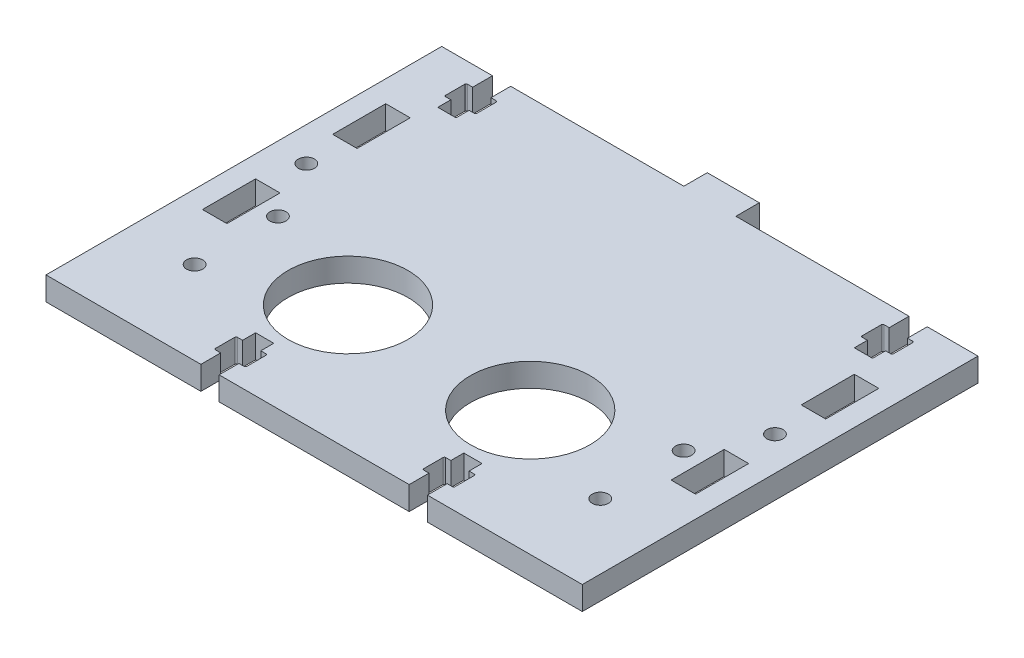
SolidWorks part; units mm, degrees
ref_plane "Front Plane" through (0, 0, 0) normal (0, 0, 1) x (1, 0, 0)
ref_plane "Top Plane" through (0, 0, 0) normal (0, 1, 0) x (1, 0, 0)
ref_plane "Right Plane" through (0, 0, 0) normal (1, 0, 0) x (0, 0, -1)
sketch "Sketch1" plane through (0, 0, 0) normal (0, 1, 0) x (1, 0, 0)
  line L1 (-51.5, 38) -> (51.5, 38)
  line L2 (-51.5, 38) -> (-51.5, -38)
  line L3 (-51.5, -38) -> (51.5, -38)
  line L4 (51.5, 38) -> (51.5, -38)
  line L5 (-51.5, 38) -> (51.5, -38) construction
  line L6 (-51.5, -38) -> (51.5, 38) construction
  point P0 (0, 0)
  dimension "D1" = 103
  dimension "D2" = 76
extrude "MainShape" add sketch "Sketch1" along normal blind 4.5
sketch "Sketch2" plane through (0, 4.5, 0) normal (0, 1, 0) x (1, 0, 0)
  line L0 (0, -38) -> (0, 38) construction
  line L1 (-51.5, -38) -> (51.5, -38) construction
  line L2 (51.5, 38) -> (-51.5, 38) construction
  line L4 (-5, 42.5) -> (5, 42.5)
  line L5 (-5, 42.5) -> (-5, 33.5)
  line L6 (-5, 33.5) -> (5, 33.5)
  line L7 (5, 42.5) -> (5, 33.5)
  line L8 (-5, 42.5) -> (5, 33.5) construction
  line L9 (-5, 33.5) -> (5, 42.5) construction
  dimension "D2" = 4.5
extrude "Tab1" add sketch "Sketch2" against normal through all
sketch "Sketch4" plane through (0, 4.5, 0) normal (0, 1, 0) x (1, 0, 0)
  line L0 (0, 42.5) -> (0, -38) construction
  line L1 (5, 42.5) -> (-5, 42.5) construction
  line L2 (-51.5, -38) -> (51.5, -38) construction
  line L3 (-40, 38) -> (-40, 27.5) construction
  line L4 (-5, 38) -> (-51.5, 38) construction
  line L5 (-38.25, 27.5) -> (-41.75, 27.5) construction
  line L6 (-41.75, 27.5) -> (-41.75, 38) construction
  line L7 (-38.25, 27.5) -> (-41.75, 27.5)
  line L8 (-41.75, 27.5) -> (-41.75, 30)
  line L9 (-41.75, 30) -> (-42.75, 30)
  line L10 (-43, 30.25) -> (-43, 33.95)
  line L11 (-42.75, 34.2) -> (-41.75, 34.2)
  line L12 (-41.75, 34.2) -> (-41.75, 38)
  line L13 (-41.75, 38) -> (-38.25, 38)
  line L14 (-38.25, 27.5) -> (-38.25, 38) construction
  line L15 (-38.25, 34.2) -> (-38.25, 38)
  line L16 (-37.25, 34.2) -> (-38.25, 34.2)
  line L17 (-37, 30.25) -> (-37, 33.95)
  line L18 (-38.25, 30) -> (-37.25, 30)
  line L19 (-38.25, 27.5) -> (-38.25, 30)
  line L20 (38.25, 27.5) -> (38.25, 38) construction
  line L21 (41.75, 27.5) -> (41.75, 38) construction
  line L22 (38.25, 27.5) -> (41.75, 27.5) construction
  line L23 (40, 38) -> (40, 27.5) construction
  line L24 (38.25, 27.5) -> (38.25, 30)
  line L25 (38.25, 30) -> (37.25, 30)
  line L26 (37, 30.25) -> (37, 33.95)
  line L27 (37.25, 34.2) -> (38.25, 34.2)
  line L28 (38.25, 34.2) -> (38.25, 38)
  line L29 (41.75, 38) -> (38.25, 38)
  line L30 (41.75, 34.2) -> (41.75, 38)
  line L31 (42.75, 34.2) -> (41.75, 34.2)
  line L32 (43, 30.25) -> (43, 33.95)
  line L33 (41.75, 30) -> (42.75, 30)
  line L34 (41.75, 27.5) -> (41.75, 30)
  line L35 (38.25, 27.5) -> (41.75, 27.5)
  arc A0 (-42.75, 30) -> (-43, 30.25) centre (-42.75, 30.25) cw
  arc A1 (-37, 30.25) -> (-37.25, 30) centre (-37.25, 30.25) cw
  arc A2 (-37.25, 34.2) -> (-37, 33.95) centre (-37.25, 33.95) cw
  arc A3 (-43, 33.95) -> (-42.75, 34.2) centre (-42.75, 33.95) cw
  arc A4 (43, 33.95) -> (42.75, 34.2) centre (42.75, 33.95) ccw
  arc A5 (37.25, 34.2) -> (37, 33.95) centre (37.25, 33.95) ccw
  arc A6 (37, 30.25) -> (37.25, 30) centre (37.25, 30.25) ccw
  arc A7 (42.75, 30) -> (43, 30.25) centre (42.75, 30.25) ccw
  point P24 (-43, 30)
  point P27 (-37, 30)
  point P30 (-37, 34.2)
  point P33 (-43, 34.2)
  point P56 (43, 34.2)
  point P57 (37, 34.2)
  point P58 (37, 30)
  point P59 (43, 30)
  dimension "D7" = 0.25
  dimension "D1" = 10.5
  dimension "D2" = 1.75
  dimension "D3" = 4.2
  dimension "D4" = 3
  dimension "D5" = 8
  dimension "D6" = 40
extrude "Cut-Extrude2" cut sketch "Sketch4" against normal through all
sketch "Sketch5" plane through (0, 4.5, 0) normal (0, 1, 0) x (1, 0, 0)
  line L0 (0, -38) -> (0, 42.5) construction
  line L1 (-51.5, -38) -> (51.5, -38) construction
  line L2 (5, 42.5) -> (-5, 42.5) construction
  line L3 (45, 38) -> (45, -38) construction
  line L4 (51.5, 38) -> (41.75, 38) construction
  line L5 (-45, 38) -> (-45, -38) construction
  line L6 (42.65, 23.1) -> (47.35, 23.1)
  line L7 (42.65, 23.1) -> (42.65, 12.9)
  line L8 (42.65, 12.9) -> (47.35, 12.9)
  line L9 (47.35, 23.1) -> (47.35, 12.9)
  line L10 (42.65, 23.1) -> (47.35, 12.9) construction
  line L11 (42.65, 12.9) -> (47.35, 23.1) construction
  line L12 (-42.65, 12.9) -> (-47.35, 23.1) construction
  line L13 (-42.65, 23.1) -> (-47.35, 12.9) construction
  line L14 (-47.35, 23.1) -> (-47.35, 12.9)
  line L15 (-42.65, 12.9) -> (-47.35, 12.9)
  line L16 (-42.65, 23.1) -> (-42.65, 12.9)
  line L17 (-42.65, 23.1) -> (-47.35, 23.1)
  line L18 (-51.5, 5.5) -> (51.5, 5.5) construction
  line L19 (-51.5, 38) -> (-51.5, -38) construction
  line L20 (51.5, -38) -> (51.5, 38) construction
  line L21 (-42.65, -12.1) -> (-47.35, -1.9) construction
  line L22 (-42.65, -1.9) -> (-47.35, -12.1) construction
  line L23 (42.65, -1.9) -> (47.35, -12.1) construction
  line L24 (42.65, -12.1) -> (47.35, -1.9) construction
  line L25 (-42.65, -12.1) -> (-47.35, -12.1)
  line L26 (-42.65, -12.1) -> (-42.65, -1.9)
  line L27 (-42.65, -1.9) -> (-47.35, -1.9)
  line L28 (-47.35, -12.1) -> (-47.35, -1.9)
  line L29 (47.35, -12.1) -> (47.35, -1.9)
  line L30 (42.65, -1.9) -> (47.35, -1.9)
  line L31 (42.65, -12.1) -> (42.65, -1.9)
  line L32 (42.65, -12.1) -> (47.35, -12.1)
  line L33 (-42.65, 23.1) -> (-47.35, 12.9) construction
  circle A0 centre (45, 5.5) radius 1.55
  circle A1 centre (-45, 5.5) radius 1.55
  point P10 (45, 18)
  point P21 (-45, 18)
  point P36 (-45, -7)
  point P37 (45, -7)
  dimension "D6" = 3.1
  dimension "D1" = 45
  dimension "D2" = 10.2
  dimension "D3" = 4.7
  dimension "D4" = 20
  dimension "D5" = 25
extrude "Cut-Extrude3" cut sketch "Sketch5" against normal through all
sketch "Sketch6" plane through (0, 4.5, 0) normal (0, 1, 0) x (1, 0, 0)
  line L0 (-17.5, -28) -> (-17.5, 28) construction
  line L2 (5, 42.5) -> (-5, 42.5) construction
  line L3 (-51.5, -14) -> (51.5, -14) construction
  line L4 (-51.5, 38) -> (-51.5, -38) construction
  line L5 (51.5, -38) -> (51.5, 38) construction
  line L6 (51.5, 38) -> (41.75, 38) construction
  line L7 (-51.5, -38) -> (51.5, -38) construction
  line L9 (-51.5, 38) -> (51.5, 38) construction
  circle A0 centre (-17.5, -14) radius 11.5
  point P4 (0, 42.5)
  dimension "D1" = 23
  dimension "D2" = 52
  dimension "D4" = 17.5
extrude "Cut-Extrude4" cut sketch "Sketch6" against normal through all
sketch "Sketch8" plane through (0, 4.5, 0) normal (0, 1, 0) x (1, 0, 0)
  line L0 (-17.5, -2.5) -> (-17.5, -25.5) construction
  line L1 (-17.5, -14) -> (-38.96, -14) construction
  line L2 (-38.96, -22) -> (-38.96, -6) construction
  line L3 (-17.5, -25.5) -> (-17.5, -2.5) construction
  circle A0 centre (-38.96, -6) radius 1.55
  circle A1 centre (-17.5, -14) radius 11.5 construction
  circle A2 centre (-38.96, -22) radius 1.55
  dimension "D3" = 3.1
  dimension "D1" = 0
  dimension "D4" = 21.46
extrude "Cut-Extrude6" cut sketch "Sketch8" against normal through all
sketch "Sketch9" plane through (0, 4.5, 0) normal (0, 1, 0) x (1, 0, 0)
  line L0 (0, -38) -> (0, 42.5) construction
  line L1 (-51.5, -38) -> (51.5, -38) construction
  line L2 (5, 42.5) -> (-5, 42.5) construction
  line L3 (20, -38) -> (20, -27.5) construction
  line L4 (18.25, -27.5) -> (21.75, -27.5) construction
  line L5 (21.75, -27.5) -> (21.75, -38) construction
  line L6 (21.75, -38) -> (21.75, -34.2)
  line L7 (21.75, -34.2) -> (22.75, -34.2)
  line L8 (23, -33.95) -> (23, -30.25)
  line L9 (22.75, -30) -> (21.75, -30)
  line L10 (21.75, -30) -> (21.75, -27.5)
  line L11 (21.75, -27.5) -> (18.25, -27.5)
  line L12 (21.75, -38) -> (18.25, -38)
  line L13 (18.25, -27.5) -> (18.25, -38) construction
  line L14 (18.25, -30) -> (18.25, -27.5)
  line L15 (17.25, -30) -> (18.25, -30)
  line L16 (17, -33.95) -> (17, -30.25)
  line L17 (18.25, -34.2) -> (17.25, -34.2)
  line L18 (18.25, -38) -> (18.25, -34.2)
  line L19 (-18.25, -27.5) -> (-18.25, -38) construction
  line L20 (-21.75, -27.5) -> (-21.75, -38) construction
  line L21 (-18.25, -27.5) -> (-21.75, -27.5) construction
  line L22 (-20, -38) -> (-20, -27.5) construction
  line L23 (-18.25, -38) -> (-18.25, -34.2)
  line L24 (-18.25, -34.2) -> (-17.25, -34.2)
  line L25 (-17, -33.95) -> (-17, -30.25)
  line L26 (-17.25, -30) -> (-18.25, -30)
  line L27 (-18.25, -30) -> (-18.25, -27.5)
  line L28 (-21.75, -38) -> (-18.25, -38)
  line L29 (-21.75, -27.5) -> (-18.25, -27.5)
  line L30 (-21.75, -30) -> (-21.75, -27.5)
  line L31 (-22.75, -30) -> (-21.75, -30)
  line L32 (-23, -33.95) -> (-23, -30.25)
  line L33 (-21.75, -34.2) -> (-22.75, -34.2)
  line L34 (-21.75, -38) -> (-21.75, -34.2)
  arc A0 (22.75, -34.2) -> (23, -33.95) centre (22.75, -33.95) ccw
  arc A1 (23, -30.25) -> (22.75, -30) centre (22.75, -30.25) ccw
  arc A2 (17, -30.25) -> (17.25, -30) centre (17.25, -30.25) cw
  arc A3 (17.25, -34.2) -> (17, -33.95) centre (17.25, -33.95) cw
  arc A4 (-17.25, -34.2) -> (-17, -33.95) centre (-17.25, -33.95) ccw
  arc A5 (-17, -30.25) -> (-17.25, -30) centre (-17.25, -30.25) ccw
  arc A6 (-23, -30.25) -> (-22.75, -30) centre (-22.75, -30.25) cw
  arc A7 (-22.75, -34.2) -> (-23, -33.95) centre (-22.75, -33.95) cw
  point P16 (23, -34.2)
  point P19 (23, -30)
  point P30 (17, -30)
  point P31 (17, -34.2)
  point P54 (-17, -34.2)
  point P55 (-17, -30)
  point P56 (-23, -30)
  point P57 (-23, -34.2)
  dimension "D7" = 0.25
  dimension "D1" = 10.5
  dimension "D2" = 1.75
  dimension "D3" = 8
  dimension "D4" = 4.2
  dimension "D5" = 3
  dimension "D6" = 20
extrude "Cut-Extrude7" cut sketch "Sketch9" against normal through all
sketch "Sketch10" [suppressed] plane through (0, 0, 28) normal (0, 0, 1) x (1, 0, 0)
  line L0 (-55, 2.25) -> (55, 2.25) construction
  line L1 (-55, 4.5) -> (-55, 0) construction
  line L2 (55, 4.5) -> (55, 0) construction
  line L3 (-16, 4.5) -> (-16, 0) construction
  line L4 (-14.25, 4.5) -> (-17.75, 4.5) construction
  line L5 (16, 4.5) -> (16, 0) construction
  line L6 (17.75, 4.5) -> (14.25, 4.5) construction
  line L7 (17.75, 0) -> (14.25, 0) construction
  line L8 (-14.25, 0) -> (-17.75, 0) construction
  circle A0 centre (-16, 2.25) radius 1.6
  circle A1 centre (16, 2.25) radius 1.6
  dimension "D1" = 3.2
  dimension "D2" = 3.2
mirror "Mirror1" about plane through (0, 0, 0) normal (1, 0, 0) of "Cut-Extrude6", "Cut-Extrude4"
equation "\"X-ROD-SPACING\"=45"
equation "\"Y-ROD-SPACING\"=75"
equation "\"Z-ROD-SPACING\"=17.5"
equation "\"Y-BED-OFFSET\"=2"
equation "\"Y-BED-ROD-INSET\"=3.5"
equation "\"Y-BED-SCREW-SPACING\"=209"
equation "\"Y-BED-SCREW-CUTOUT-SLOT-HEIGHT\"=2"
equation "\"T-SLOT-NUT-FILLET-RADIUS\"=0.25"
equation "\"T-SLOT-SCREW-SHAFT-RADIUS\"=1.75"
equation "\"T-SLOT-SCREW-SHAFT-CUTOUT-LENGTH\"=10.5"
equation "\"T-SLOT-NUT-DEPTH\"=4.2"
equation "\"T-SLOT-NUT-WIDTH\"=3"
equation "\"T-SLOT-NUT-END-DISTANCE\"=8"
equation "\"ACRYLIC-THICKNESS\"=10"
equation "\"ACRYLIC-THICKNESS2\"=4.5"
equation "\"ACRYLIC-TAB-CUTOUT-SIZE\"=\"ACRYLIC-THICKNESS\"+\"ACRYLIC-TAB-TOLERANCE\"*2"
equation "\"ACRYLIC-TAB-WIDTH\"=\"ACRYLIC-THICKNESS\""
equation "\"ACRYLIC-M3-HOLE\"=3.1"
equation "\"SMOOTHROD-CAP-SCREW-DISTANCE\"=20"
equation "\"FRAME-WIDTH-INNER\"=370"
equation "\"NEMA17-HOLE-SPACING\"=31"
equation "\"NEMA17-CENTRAL-CUTOUT\"=22.5"
equation "\"Z-BRACKET-REACH\"=55"
equation "\"Z-ROD-INSET\"=16"
equation "\"TOP-BRACKET-SPACING\"=40"
equation "\"SMOOTHROD-X-LENGTH\"=350"
equation "\"SMOOTHROD-Y-LENGTH\"=350"
equation "\"SMOOTHROD-Z-LENGTH\"=350"
equation "\"SMOOTHROD-TIGHTENING-HEADROOM\"=.25"
equation "\"LEADSCREW-Z-LENGTH\"=300"
equation "\"SCREW-LENGTH-FRAME\"=\"ACRYLIC-THICKNESS\" + 10"
equation "\"SCREW-LENGTH-MOTOR\"=\"ACRYLIC-THICKNESS\" + 5"
equation "\"SCREW-LENGTH-EXTRUDER\"=28"
equation "\"SCREW-HEAD-RADIUS\"=6"
equation "\"PRINTED-X-SMOOTHROD-DIAMETER\"=8.2"
equation "\"PRINTED-X-SMOOTHROD-CUTOUT\"=10"
equation "\"PRINTED-X-BASE-HEIGHT\"=10"
equation "\"PRINTED-LM8UU-CUTOUT-SIZE\"=15.25"
equation "\"PRINTED-LM8UU-CUTOUT-LENGTH\"=24.5"
equation "\"PRINTED-X-IDLER-HEIGHT\"=16"
equation "\"PSU-MOUNTING-WIDTH\"=95"
equation "\"PSU-MOUNTING-HEIGHT\"=177"
equation "\"Y-BELT-TO-ROD-DISTANCE\"=20"
equation "\"SPOOL-HOLDER-ROD-SPACING\"=150"
equation "\"ACRYLIC-X-CARRIAGE-WIDTH\"=55"
equation "\"ACRYLIC-X-CARRIAGE-HEIGHT\"=75"
equation "\"ACRYLIC-X-CARRIAGE-SCREW-SPACING-X\"=15"
equation "\"ACRYLIC-X-CARRIAGE-SCREW-SPACING-Y\"=33"
equation "\"ACRYLIC-X-CARRIAGE-CENTER-TAB-SPACING\"=14"
equation "\"D1@MainShape\" = \"ACRYLIC-THICKNESS2\""
equation "\"D1@Sketch2\"=\"ACRYLIC-TAB-WIDTH\""
equation "\"D2@Sketch2\"=\"ACRYLIC-THICKNESS2\""
equation "\"D1@Sketch4\"=\"T-SLOT-SCREW-SHAFT-CUTOUT-LENGTH\""
equation "\"D2@Sketch4\"=\"T-SLOT-SCREW-SHAFT-RADIUS\""
equation "\"D3@Sketch4\"=\"T-SLOT-NUT-DEPTH\""
equation "\"D4@Sketch4\"=\"T-SLOT-NUT-WIDTH\""
equation "\"D5@Sketch4\"=\"T-SLOT-NUT-END-DISTANCE\""
equation "\"D7@Sketch4\"=\"T-SLOT-NUT-FILLET-RADIUS\""
equation "\"ACRYLIC-X-CARRIAGE-EXTRUDER-SHELF-DEPTH\"=\"ACRYLIC-X-CARRIAGE-EXTRUDER-OFFSET\" + 28"
equation "\"ACRYLIC-X-CARRIAGE-LM8UU-CUTOUT-WIDTH\"=24.25"
equation "\"ACRYLIC-X-CARRIAGE-EXTRUDER-BRACE-SPACING\"=23"
equation "\"ACRYLIC-X-CARRIAGE-EXTRUDER-BRACE-TAB-OFFSET\"=20"
equation "\"ACRYLIC-X-CARRIAGE-EXTRUDER-BRACE-HEIGHT\"=35"
equation "\"ACRYLIC-X-CARRIAGE-EXTRUDER-BRACE-SCREW-SPACING\"=22"
equation "\"D2@Sketch5\"=\"ACRYLIC-TAB-CUTOUT-SIZE\""
equation "\"D3@Sketch5\"=\"ACRYLIC-THICKNESS2\"+\"ACRYLIC-TAB-TOLERANCE\"*2"
equation "\"D4@Sketch5\"=\"ACRYLIC-X-CARRIAGE-EXTRUDER-BRACE-TAB-OFFSET\""
equation "\"D3@Sketch8\"=\"ACRYLIC-M3-HOLE\""
equation "\"ACRYLIC-X-CARRIAGE-EXTRUDER-ANGLE\"=90"
equation "\"ACRYLIC-X-CARRIAGE-EXTRUDER-OFFSET\"=26"
equation "\"D6@Sketch5\"=\"ACRYLIC-M3-HOLE\""
equation "\"D1@Sketch9\"=\"T-SLOT-SCREW-SHAFT-CUTOUT-LENGTH\""
equation "\"D2@Sketch9\"=\"T-SLOT-SCREW-SHAFT-RADIUS\""
equation "\"D3@Sketch9\"=\"T-SLOT-NUT-END-DISTANCE\""
equation "\"D4@Sketch9\"=\"T-SLOT-NUT-DEPTH\""
equation "\"D5@Sketch9\"=\"T-SLOT-NUT-WIDTH\""
equation "\"D7@Sketch9\"=\"T-SLOT-NUT-FILLET-RADIUS\""
equation "\"ACRYLIC-TAB-TOLERANCE\"=.1"
equation "\"ACRYLIC-X-CARRIAGE-DUAL-WIDTH-MULTIPLIER\"=1.65"
equation "\"ACRYLIC-X-CARRIAGE-DUAL-HOTEND-SPACING\"=42"
equation "\"ACRYLIC-X-CARRIAGE-DUAL-WIDTH\"=103"
equation "\"ACRYLIC-X-CARRIAGE-DUAL-HOTEND-SEPARATION\"=35"
equation "\"ACRYLIC-X-CARRIAGE-DUAL-MOUNT-PLATE-DEPTH\"=76"
equation "\"ACRYLIC-X-CARRIAGE-DUAL-MOUNT-BRACE-WIDTH\"=45"
equation "\"D1@Sketch5\"=\"ACRYLIC-X-CARRIAGE-DUAL-MOUNT-BRACE-WIDTH\""
equation "\"ACRYLIC-X-CARRIAGE-DUAL-MOUNT-SCREW-WIDTH\"=40"
equation "\"D6@Sketch4\"=\"ACRYLIC-X-CARRIAGE-DUAL-MOUNT-SCREW-WIDTH\""
equation "\"D1@Sketch1\"=\"ACRYLIC-X-CARRIAGE-DUAL-WIDTH\""
equation "\"D2@Sketch1\"=\"ACRYLIC-X-CARRIAGE-DUAL-MOUNT-PLATE-DEPTH\""
equation "\"D4@Sketch6\"=\"ACRYLIC-X-CARRIAGE-DUAL-HOTEND-SEPARATION\"/2"
